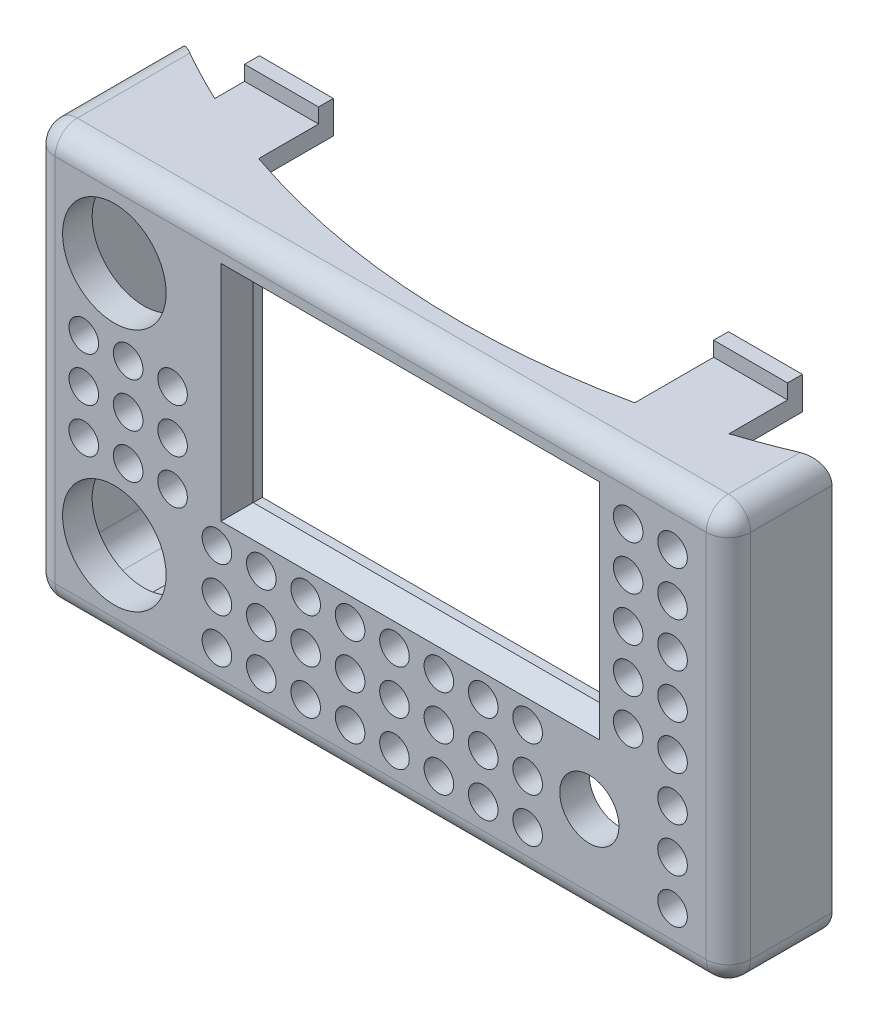
SolidWorks part; units mm, degrees
ref_plane "前视基准面" through (0, 0, 0) normal (0, 0, 1) x (1, 0, 0)
ref_plane "上视基准面" through (0, 0, 0) normal (0, 1, 0) x (1, 0, 0)
ref_plane "右视基准面" through (0, 0, 0) normal (1, 0, 0) x (0, 0, -1)
sketch "草图1" plane through (0, 0, 0) normal (0, 0, 1) x (1, 0, 0)
  line L1 (-23.5, 14) -> (23.5, 14)
  line L2 (-23.5, 14) -> (-23.5, -14)
  line L3 (-23.5, -14) -> (23.5, -14)
  line L4 (23.5, 14) -> (23.5, -14)
  line L5 (-23.5, 14) -> (23.5, -14) construction
  line L6 (-23.5, -14) -> (23.5, 14) construction
  point P0 (0, 0)
extrude "凸台-拉伸1" add sketch "草图1" along normal blind 10
sketch "草图4" plane through (0, 0, 0) normal (0, 0, -1) x (-1, 0, 0)
  line L1 (-22.5, 13) -> (22.5, 13)
  line L2 (-22.5, 13) -> (-22.5, -13)
  line L3 (-22.5, -13) -> (22.5, -13)
  line L4 (22.5, 13) -> (22.5, -13)
  line L5 (-22.5, 13) -> (22.5, -13) construction
  line L6 (-22.5, -13) -> (22.5, 13) construction
  point P0 (0, 0)
extrude "切除-拉伸4" cut sketch "草图4" against normal blind 8
sketch "草图2" plane through (0, 14, 0) normal (0, 1, 0) x (1, 0, 0)
  line L0 (-23.5, -10) -> (-23.5, 0) construction
  line L1 (23.5, -10) -> (23.5, -3) construction
  line L2 (23.5, -10) -> (23.5, 0) construction
  line L3 (23.5, -3) -> (-23.5, 0) construction
  line L4 (0, -1.5) -> (4.1617, 63.7003) construction
  line L5 (-23.5, 0) -> (2.8097, 42.5182) construction
  arc A2 (-23.5, 0) -> (23.5, -3) centre (2.8097, 42.5182) ccw
extrude "切除-拉伸1" cut sketch "草图2" against normal blind 28 and the other way through all
fillet "圆角1" radius 1.5 12 edges at (23.5, 14, 6.5) (-23.5, -14, 5) (0, -14, 10) (23.5, -14, 6.5) (23.5, 0, 10) (0, 14, 10) (-23.5, 0, 10) (-23.5, 14, 5) (-22.5, -13, 4.3014) (-22.5, 13, 4.3014) (22.5, -13, 5.7207) (22.5, 13, 5.7207)
sketch "草图5" plane through (0, 0, 8) normal (0, 0, -1) x (-1, 0, 0)
  line L0 (0, 0) -> (-21.1837, 0) construction
  line L1 (-13.5, -12.8) -> (-13.5, -14)
  line L2 (22, 14) -> (-22, 14) construction
  line L3 (-18.5, 12.8) -> (-13.5, 12.8)
  line L4 (-18.5, 12.8) -> (-18.5, 14)
  line L5 (-18.5, 14) -> (-13.5, 14)
  line L6 (-13.5, 12.8) -> (-13.5, 14)
  line L7 (-18.5, -14) -> (-13.5, -14)
  line L8 (-18.5, -12.8) -> (-18.5, -14)
  line L9 (-18.5, -12.8) -> (-13.5, -12.8)
extrude "凸台-拉伸2" add sketch "草图5" along normal blind 8
sketch "草图8" plane through (0, 14, 0) normal (0, 1, 0) x (1, 0, 0)
  line L0 (18.5, 0) -> (18.5, -4.9561) construction
  line L1 (13.5, 0) -> (18.5, 0)
  line L2 (13.5, 0) -> (13.5, -1)
  line L3 (13.5, -1) -> (18.5, -1)
  line L4 (18.5, 0) -> (18.5, -1)
extrude "凸台-拉伸3" add sketch "草图8" along normal blind 1
sketch "草图9" plane through (0, 0, 8) normal (0, 0, -1) x (-1, 0, 0)
  line L0 (22.5, 11.5) -> (22.5, 12.8) construction
  line L1 (22.5, 12.8) -> (18.5, 12.8) construction
  line L2 (22, 14) -> (-13.5, 14) construction
  line L3 (18.5, 12.8) -> (13.4995, 12.8)
  line L4 (18.5, 12.8) -> (18.5, 14)
  line L5 (18.5, 14) -> (13.4995, 14)
  line L6 (13.4995, 12.8) -> (13.4995, 14)
  line L7 (0, 0) -> (22.5, 0) construction
  line L8 (22.5, -11.5) -> (22.5, 11.5) construction
  line L9 (13.4995, -12.8) -> (13.4995, -14)
  line L10 (18.5, -14) -> (13.4995, -14)
  line L11 (18.5, -12.8) -> (18.5, -14)
  line L12 (18.5, -12.8) -> (13.4995, -12.8)
extrude "凸台-拉伸5" add sketch "草图9" along normal blind 8.3
sketch "草图11" plane through (0, -14, 0) normal (0, -1, 0) x (1, 0, 0)
  line L0 (13.5, 0) -> (13.5, 6.3256) construction
  line L1 (18.5, 0) -> (13.5, 0)
  line L2 (18.5, 0) -> (18.5, 1)
  line L3 (18.5, 1) -> (13.5, 1)
  line L4 (13.5, 0) -> (13.5, 1)
extrude "凸台-拉伸6" add sketch "草图11" along normal blind 1
sketch "草图12" plane through (0, 14, 0) normal (0, 1, 0) x (1, 0, 0)
  line L0 (-13.4995, 0.3) -> (-13.4995, -4.7471) construction
  line L1 (-18.5, 0.3) -> (-13.4995, 0.3)
  line L2 (-18.5, 0.3) -> (-18.5, -0.7)
  line L3 (-18.5, -0.7) -> (-13.4995, -0.7)
  line L4 (-13.4995, 0.3) -> (-13.4995, -0.7)
extrude "凸台-拉伸7" add sketch "草图12" along normal blind 1
sketch "草图14" plane through (0, -14, 0) normal (0, -1, 0) x (1, 0, 0)
  line L0 (-18.5, -0.3) -> (-18.5, 2.7134) construction
  line L1 (-13.4995, -0.3) -> (-18.5, -0.3)
  line L2 (-13.4995, -0.3) -> (-13.4995, 0.7)
  line L3 (-13.4995, 0.7) -> (-18.5, 0.7)
  line L4 (-18.5, -0.3) -> (-18.5, 0.7)
extrude "凸台-拉伸8" add sketch "草图14" along normal blind 1
sketch "草图15" plane through (0, 0, 10) normal (0, 0, 1) x (1, 0, 0)
  line L0 (-22, -12.5) -> (-18, -12.5) construction
  line L1 (-22, -12.5) -> (22, -12.5) construction
  line L2 (-18, -12.5) -> (-18, -8.2492) construction
  line L3 (0, 0) -> (-18.9499, 0) construction
  line L4 (-18, -8.2492) -> (14.1007, -8.2492) construction
  line L5 (14.1007, -8.2492) -> (14.1007, -7.65) construction
  line L6 (-18, -8.2492) -> (-10, -8.2492) construction
  line L7 (-10, -8.2492) -> (-10, -2.4492) construction
  line L9 (-10, -2.4492) -> (14, -2.4492)
  line L10 (-10, -2.4492) -> (-10, 11.0508)
  line L11 (-10, 11.0508) -> (14, 11.0508)
  line L12 (14, -2.4492) -> (14, 11.0508)
  circle A0 centre (-18, -8.2492) radius 3.5
  circle A1 centre (-18, 8.2492) radius 3.5
  circle A2 centre (14.1007, -7.65) radius 2
extrude "切除-拉伸5" cut sketch "草图15" against normal blind 2
sketch "草图16" plane through (0, 0, 10) normal (0, 0, 1) x (1, 0, 0)
  line L0 (-17.0666, 0) -> (-17.0666, -5.9093) construction
  line L1 (-17.0666, 0) -> (-14.816, 0) construction
  line L2 (-17.0666, 0) -> (-10.4099, 0) construction
  circle A0 centre (-17.0666, 0) radius 1
  circle A1 centre (-14.0666, 0) radius 1
  circle A2 centre (-14.0666, 3) radius 1
  circle A3 centre (-17.0666, 3) radius 1
  circle A4 centre (-17.0666, -3) radius 1
  circle A5 centre (-14.0666, -3) radius 1
  circle A9 centre (-20.0666, 0) radius 1
  circle A10 centre (-20.0666, -3) radius 1
  circle A11 centre (-20.0666, 3) radius 1
  dimension "D1" = 2
  dimension "D2" = 2
extrude "切除-拉伸6" cut sketch "草图16" against normal blind 2
sketch "草图17" plane through (0, 0, 10) normal (0, 0, 1) x (1, 0, 0)
  circle A0 centre (-11.0681, -10.8073) radius 1
  circle A1 centre (-8.0681, -10.8073) radius 1
  circle A2 centre (-5.0681, -10.8073) radius 1
  circle A3 centre (-2.0681, -10.8073) radius 1
  circle A4 centre (0.9319, -10.8073) radius 1
  circle A5 centre (3.9319, -10.8073) radius 1
  circle A6 centre (6.9319, -10.8073) radius 1
  circle A7 centre (9.9319, -10.8073) radius 1
  circle A8 centre (-8.0681, -7.8073) radius 1
  circle A9 centre (-5.0681, -7.8073) radius 1
  circle A10 centre (-2.0681, -7.8073) radius 1
  circle A11 centre (0.9319, -7.8073) radius 1
  circle A12 centre (3.9319, -7.8073) radius 1
  circle A13 centre (6.9319, -7.8073) radius 1
  circle A14 centre (9.9319, -7.8073) radius 1
  circle A15 centre (-8.0681, -4.8073) radius 1
  circle A16 centre (-5.0681, -4.8073) radius 1
  circle A17 centre (-2.0681, -4.8073) radius 1
  circle A18 centre (0.9319, -4.8073) radius 1
  circle A19 centre (3.9319, -4.8073) radius 1
  circle A20 centre (6.9319, -4.8073) radius 1
  circle A21 centre (9.9319, -4.8073) radius 1
  circle A22 centre (-11.0681, -7.8073) radius 1
  circle A23 centre (-11.0681, -4.8073) radius 1
  dimension "D1" = 8
  dimension "D2" = 3
extrude "切除-拉伸7" cut sketch "草图17" against normal blind 2
sketch "草图18" plane through (0, 0, 10) normal (0, 0, 1) x (1, 0, 0)
  line L0 (19.7237, -1.6411) -> (16.7237, -1.6411) construction
  circle A0 centre (16.7237, -1.6411) radius 1
  circle A1 centre (19.7237, -1.6411) radius 1
  circle A2 centre (19.7237, 1.3589) radius 1
  circle A3 centre (19.7237, 4.3589) radius 1
  circle A4 centre (19.7237, 7.3589) radius 1
  circle A5 centre (19.7237, 10.3589) radius 1
  circle A6 centre (16.7237, 1.3589) radius 1
  circle A7 centre (16.7237, 4.3589) radius 1
  circle A8 centre (16.7237, 7.3589) radius 1
  circle A9 centre (16.7237, 10.3589) radius 1
  circle A11 centre (19.7237, -10.6411) radius 1
  circle A12 centre (19.7237, -7.6411) radius 1
  circle A13 centre (19.7237, -4.6411) radius 1
  dimension "D1" = 2
  dimension "D2" = 5
extrude "切除-拉伸8" cut sketch "草图18" against normal blind 2
chamfer "倒角1" distance 0.8 angle 60 4 edges at (2, -2.4492, 10) (14, 4.3008, 10) (2, 11.0508, 10) (-10, 4.3008, 10) first distance on face at (17.7237, 4.3589, 10)
fillet "圆角2" radius 0.5 12 edges at (-19.75, -13, 8) (-22.0607, -12.5607, 8) (-19.75, 13, 8) (-22.0607, 12.5607, 8) (19.75, 13, 8) (22.0607, 12.5607, 8) (19.75, -13, 8) (22.0607, -12.5607, 8) (0.0002, -13, 8) (-22.5, 0, 8) (0.0002, 13, 8) (22.5, 0, 8)
sketch "草图3" plane through (0, 0, 0) normal (0, 0, 1) x (1, 0, 0)
  line L1 (22.5, 13) -> (-22.5, 13)
  line L2 (22.5, 13) -> (22.5, -13)
  line L3 (22.5, -13) -> (-22.5, -13)
  line L4 (-22.5, 13) -> (-22.5, -13)
  line L5 (22.5, 13) -> (-22.5, -13) construction
  line L6 (22.5, -13) -> (-22.5, 13) construction
  point P0 (0, 0)
